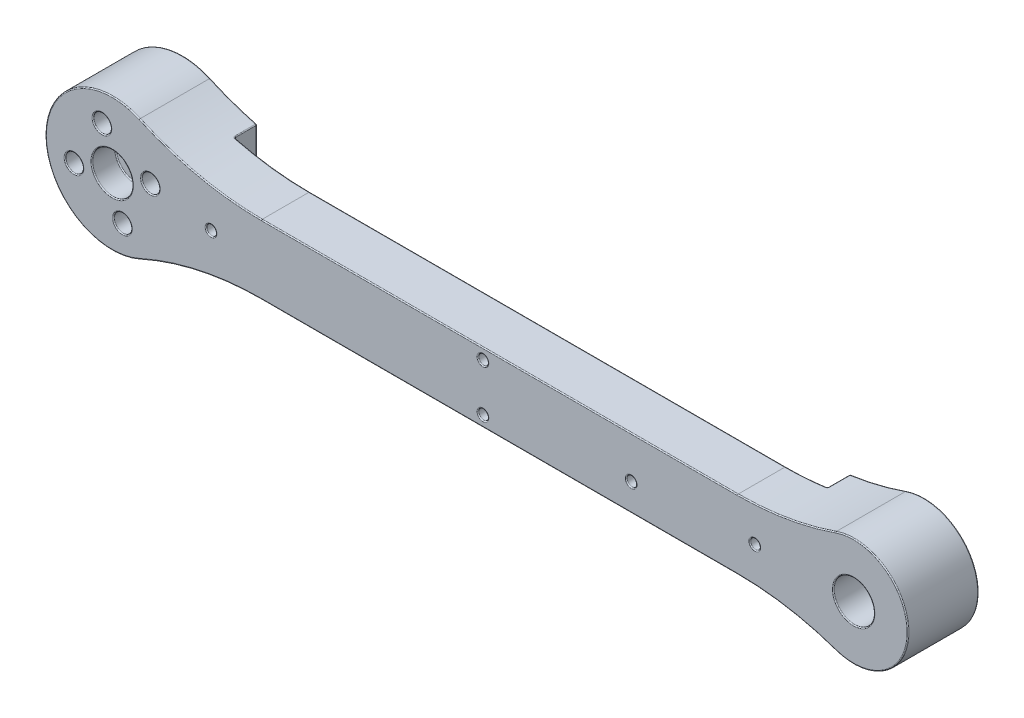
SolidWorks part; units mm, degrees
ref_plane "정면" through (0, 0, 0) normal (0, 0, 1) x (1, 0, 0)
ref_plane "윗면" through (0, 0, 0) normal (0, 1, 0) x (1, 0, 0)
ref_plane "우측면" through (0, 0, 0) normal (1, 0, 0) x (0, 0, -1)
sketch "스케치1" plane through (0, 0, 0) normal (0, 0, 1) x (1, 0, 0)
  line L0 (0, 11) -> (50, 11)
  line L1 (50, 11) -> (50, -11)
  line L2 (50, -11) -> (0, -11)
  line L3 (0, 0) -> (78.6227, 0) construction
  line L4 (8.4853, 7) -> (50, 7)
  line L5 (8.4853, -7) -> (50, -7)
  line L6 (0, 0) -> (25.6752, -44.4707) construction
  line L7 (2.0706, -7.7274) -> (0, 0) construction
  line L8 (0, 11) -> (0, -11) construction
  arc A0 (0, 11) -> (0, -11) centre (0, 0) ccw
  circle A1 centre (0, 0) radius 4.1
  circle A6 centre (0, 0) radius 11
  circle A7 centre (2.0706, -7.7274) radius 1.8
  circle A8 centre (-7.7274, -2.0706) radius 1.8
  circle A9 centre (-2.0706, 7.7274) radius 1.8
  circle A10 centre (7.7274, 2.0706) radius 1.8
  point P15 (0, 0)
  point P26 (0, 0)
  dimension "D1" = 22
  dimension "D2" = 3.6
  dimension "D4" = 8.2
  dimension "D3" = 8
  dimension "D6" = 50
  dimension "D7" = 14
  dimension "D8" = 60
  dimension "D5" = 15
  dimension "D9" = 4
extrude "보스-돌출1" add sketch "스케치1" along normal blind 14.3 contours A6 A0 A10 A9 A8 A7 A1 | A6 L5 L1 L4 region at (4.5578, 9.6684, 0) region at (30.0954, 0, 0)
sketch "스케치3" plane through (0, 0, 0) normal (0, 0, -1) x (-1, 0, 0)
  circle A0 centre (0, 0) radius 4.1
  circle A1 centre (0, 0) radius 2.45
  circle M6 centre (0, 0) radius 4.1
  dimension "D1" = 8.2
  dimension "D2" = 4.9
extrude "보스-돌출2" add sketch "스케치3" against normal blind 9.5 contours A1 M6 region at (3.984, 0, 0)
sketch "스케치4" plane through (0, 0, 0) normal (0, 0, -1) x (-1, 0, 0)
  line L3 (-8.4853, 7) -> (-50, 7)
  line L4 (-50, 7) -> (-50, -7)
  line L5 (-50, -7) -> (-8.4853, -7)
  line L6 (-8.4853, 7) -> (-50, 7)
  line L7 (-50, 7) -> (-50, -7)
  line L8 (-50, -7) -> (-8.4853, -7)
  arc A0 (-0.9294, 7.7274) -> (5.0706, 7.7274) centre (2.0706, 7.7274) ccw
  circle A1 centre (-7.7274, 2.0706) radius 1.8
  circle A2 centre (-7.7274, 2.0706) radius 1.8
  circle A3 centre (2.0706, 7.7274) radius 1.8
  circle A4 centre (2.0706, 7.7274) radius 1.8
  circle A5 centre (7.7274, -2.0706) radius 1.8
  circle A6 centre (7.7274, -2.0706) radius 1.8
  circle A7 centre (-2.0706, -7.7274) radius 1.8
  circle A8 centre (-2.0706, -7.7274) radius 1.8
  circle A9 centre (0, 0) radius 2.45
  circle A10 centre (0, 0) radius 2.45
  arc A11 (7.7274, 0.9294) -> (7.7274, -5.0706) centre (7.7274, -2.0706) ccw
  circle A12 centre (-7.7274, 2.0706) radius 3
  arc A13 (0.9294, -7.7274) -> (-5.0706, -7.7274) centre (-2.0706, -7.7274) ccw
  circle A14 centre (0, 0) radius 13.5
  circle A15 centre (2.0706, 7.7274) radius 3
  circle A16 centre (7.7274, -2.0706) radius 3
  arc A17 (-8.4853, -7) -> (-8.4853, 7) centre (0, 0) ccw
  circle A18 centre (-2.0706, -7.7274) radius 3
  circle M9 centre (-7.7274, 2.0706) radius 1.8
  circle M10 centre (2.0706, 7.7274) radius 1.8
  circle M11 centre (7.7274, -2.0706) radius 1.8
  circle M12 centre (-2.0706, -7.7274) radius 1.8
  dimension "D6" = 6
  dimension "D8" = 27
  dimension "D1" = 0
  dimension "D2" = 0
  dimension "D3" = 0
  dimension "D4" = 0
  dimension "D5" = 0
  dimension "D7" = 0
sketch "스케치5" plane through (0, 0, 0) normal (0, 0, -1) x (-1, 0, 0)
  line L0 (-50, 7) -> (-141.5147, 7)
  line L1 (-50, -7) -> (-141.5147, -7)
  line L2 (-50, 7) -> (-50, -7)
  circle A0 centre (-150, 0) radius 11
  circle A1 centre (-150, 0) radius 4.8
  circle A2 centre (-150, 0) radius 4.1
  line M23 (-50, 7) -> (-50, -7)
  dimension "D1" = 22
  dimension "D2" = 9.6
  dimension "D3" = 8.2
  dimension "D4" = 150
extrude "보스-돌출3" add sketch "스케치5" against normal up to surface (14.3 mm away) contours A0 L1 L0 M23 | A0 A1 | A1 A2 region at (94.9009, 0, 0) region at (139.9406, 3.6138, 0) region at (154.6642, 0, 0) up to face at (9.5274, 2.0706, 14.3)
extrude "컷-돌출6" cut sketch "스케치5<3>" against normal blind 1.8 contours A1 A2 region at (154.6642, 0, 0)
sketch "스케치5<3>" plane through (0, 0, 0) normal (0, 0, -1) x (-1, 0, 0) same geometry as "스케치5"
sketch "스케치6" plane through (0, 0, 0) normal (0, 0, -1) x (-1, 0, 0)
  line L0 (0, 0) -> (-78.6227, 0) construction
  line L1 (-135, -7) -> (-15, -7)
  line L2 (-135, -7) -> (-135, 7)
  line L3 (-135, 7) -> (-15, 7)
  line L4 (-15, -7) -> (-15, 7)
  line L5 (-135, -7) -> (-15, 7) construction
  line L6 (-135, 7) -> (-15, -7) construction
  line L7 (-125.1, 2.6) -> (-24.9, 2.6)
  line L8 (-125.1, 2.6) -> (-125.1, -2.6)
  line L9 (-125.1, -2.6) -> (-24.9, -2.6)
  line L10 (-24.9, 2.6) -> (-24.9, -2.6)
  line L11 (-125.1, 2.6) -> (-24.9, -2.6) construction
  line L12 (-125.1, -2.6) -> (-24.9, 2.6) construction
  circle A0 centre (-130, 0) radius 1
  circle A1 centre (-75, 4.8) radius 1
  circle A2 centre (-75, -4.8) radius 1
  circle A3 centre (-20, 0) radius 1
  point P0 (-75, 0)
  point P5 (-75, 0)
  line M29 (-8.4853, 7) -> (-141.5147, 7)
  line M31 (-141.5147, -7) -> (-8.4853, -7)
  dimension "D6" = 2
  dimension "D7" = 2
  dimension "D10" = 2
  dimension "D12" = 2
  dimension "D1" = 75
  dimension "D2" = 14
  dimension "D3" = 120
  dimension "D4" = 100.2
  dimension "D5" = 5.2
  dimension "D8" = 2.2
  dimension "D9" = 2.2
  dimension "D11" = 5
  dimension "D13" = 5
extrude "컷-돌출7" cut sketch "스케치6" against normal blind 4.55 contours L4 L2 A3 A2 A1 A0 L7 L10 L9 L8 M31 M29 | L10 L7 L8 L9 | A0 | A1 | A2 | A3 region at (133.7919, 0, 0) region at (75, 0, 0) region at (130, 0, 0) region at (75, 4.8, 0) region at (75, -4.8, 0) region at (20, 0, 0)
extrude "컷-돌출8" cut sketch "스케치6<3>" against normal blind 5.2 from surface contours L7 L10 L9 L8 starting at face at (75, 0, 4.55)
sketch "스케치6<3>" plane through (0, 0, 0) normal (0, 0, -1) x (-1, 0, 0) same geometry as "스케치6"
extrude "컷-돌출9" cut sketch "스케치6<4>" against normal through all contours A0 | A1 | A2 | A3
sketch "스케치6<4>" plane through (0, 0, 0) normal (0, 0, -1) x (-1, 0, 0) same geometry as "스케치6"
sketch "스케치9" plane through (0, 0, 0) normal (0, 0, -1) x (-1, 0, 0)
  line L0 (-110, 7) -> (-110, -7) construction
  line L1 (-50, 7) -> (-141.5147, 7) construction
  line L2 (-50, -7) -> (-141.5147, -7) construction
  line L3 (-135, -7) -> (-15, -7) construction
  circle A0 centre (-105, -1.5) radius 1
  dimension "D1" = 2
  dimension "D2" = 40
  dimension "D3" = 5
  dimension "D4" = 5.5
extrude "컷-돌출10" cut sketch "스케치9" against normal through all
sketch "스케치10" plane through (0, 0, 0) normal (0, 0, -1) x (-1, 0, 0)
  circle A0 centre (0, 0) radius 13.5
  circle A1 centre (0, 0) radius 11
  dimension "D1" = 27
extrude "보스-돌출4" add sketch "스케치10" against normal up to surface (14.3 mm away) from surface up to face at (104, -1.5, 14.3) starting at face at (9.5274, 2.0706, 0)
extrude "컷-돌출11" cut sketch "스케치4" against normal blind 5 from surface contours A0 A15 M10 | A16 A11 M11 | A12 M9 | A13 A18 M12 region at (4.3833, -9.502, 0) region at (-9.502, -4.3833, 0) region at (-4.3833, 9.502, 0) region at (10.6426, 2.0706, 0) starting at face at (7.0108, 0, 0)
fillet "필렛1" radius 60 4 edges at (11.5434, 7, 7.15) (11.5434, -7, 7.15) (141.5147, -7, 7.15) (141.5147, 7, 7.15)
fillet "필렛2" radius 0.2 65 edges at (135, 7.6044, 2.275) (15, 8.9625, 2.275) (15, -8.9625, 2.275) (135, -7.6044, 2.275) (3.8706, -7.7274, 5) (5.0706, -7.7274, 5) (9.5274, 2.0706, 5) (10.7274, 2.0706, 5) (-5.9274, -2.0706, 5) (-4.7274, -2.0706, 5) (-0.2706, 7.7274, 5) (0.9294, 7.7274, 5) (145.2, 0, 1.8) (145.9, 0, 1.8) (-4.1, 0, 9.5) (-2.45, 0, 9.5) (9.5274, 2.0706, 14.3) (-0.2706, 7.7274, 14.3) (-5.9274, -2.0706, 14.3) (3.8706, -7.7274, 14.3) (4.1, 0, 14.3) (154.1, 0, 14.3) (19, 0, 14.3) (74, -4.8, 14.3) (74, 4.8, 14.3) (129, 0, 14.3) (104, -1.5, 14.3) (136.5755, 7.8511, 14.3) (161, 0, 14.3) (136.5755, -7.8511, 14.3) (78.3627, -7, 14.3) (17.6032, -8.3415, 14.3) (-13.5, 0, 14.3) (17.6032, 8.3415, 14.3) (78.3627, 7, 14.3) (-4.7274, -2.0706, 0) (5.0706, -7.7274, 0) (-2.45, 0, 0) (10.2054, 10.4366, 0) (-13.5, 0, 0) (10.2054, -10.4366, 0) (15, 0, 0) (0.9294, 7.7274, 0) (10.7274, 2.0706, 0) (125.1, 0, 4.55) (75, -2.6, 4.55) (24.9, 0, 4.55) (75, 2.6, 4.55) (130.7634, 7.1513, 4.55) (78.3627, 7, 4.55) (22.547, 7.4926, 4.55) (15, 0, 4.55) (22.547, -7.4926, 4.55) (78.3627, -7, 4.55) (130.7634, -7.1513, 4.55) (135, 0, 4.55) (19, 0, 4.55) (74, -4.8, 4.55) (74, 4.8, 4.55) (129, 0, 4.55) (140.7478, -8.7149, 0) (161, 0, 0) (140.7478, 8.7149, 0) (135, 0, 0) (145.2, 0, 0)
